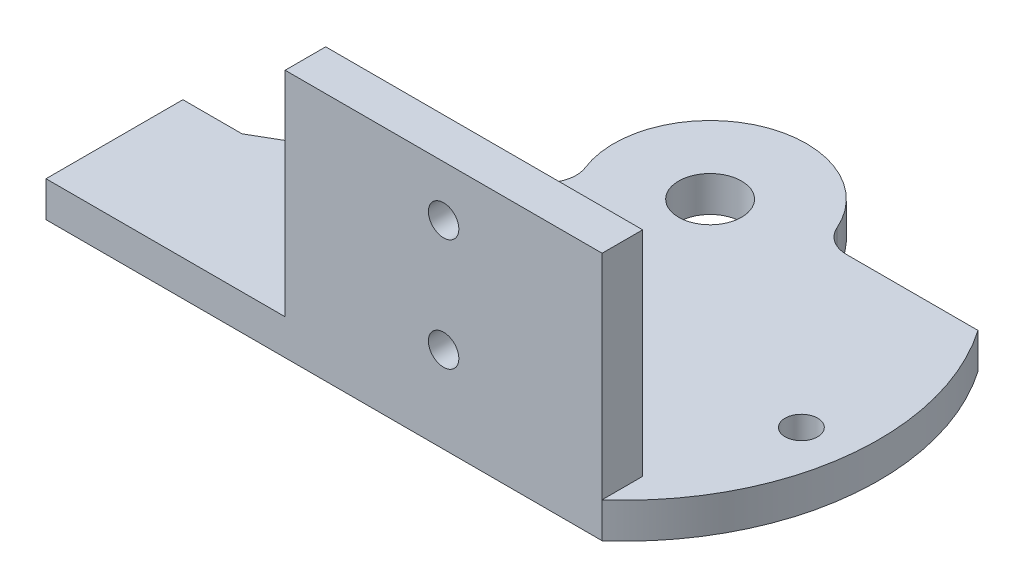
SolidWorks part; units mm, degrees
ref_plane "Alzado" through (0, 0, 0) normal (0, 0, 1) x (1, 0, 0)
ref_plane "Planta" through (0, 0, 0) normal (0, 1, 0) x (1, 0, 0)
ref_plane "Vista lateral" through (0, 0, 0) normal (1, 0, 0) x (0, 0, -1)
sketch "Croquis1" plane through (0, 0, 0) normal (0, 1, 0) x (1, 0, 0)
  line L0 (-35, 32.5) -> (35, -32.5) construction
  line L1 (-35, 32.5) -> (35, 32.5)
  line L2 (-35, 32.5) -> (-35, -32.5)
  line L3 (-35, -32.5) -> (35, -32.5)
  line L4 (35, 32.5) -> (35, -32.5)
  dimension "D1" = 70
  dimension "D2" = 65
extrude "Extruir1" add sketch "Croquis1" along normal blind 3.5
sketch "Croquis2" plane through (0, 3.5, 0) normal (0, 1, 0) x (1, 0, 0)
  line L0 (0, 32.5) -> (0, -32.5) construction
  line L1 (35, 32.5) -> (-35, 32.5) construction
  line L2 (-35, -32.5) -> (35, -32.5) construction
  circle A0 centre (0, -17.5) radius 3.1
  dimension "D1" = 6.2
  dimension "D2" = 15
extrude "Extruir2" cut sketch "Croquis2" against normal blind 5
sketch "Croquis3" plane through (0, 3.5, 0) normal (0, 1, 0) x (1, 0, 0)
  line L0 (0, -32.5) -> (0, 32.5) construction
  line L1 (-35, -32.5) -> (35, -32.5) construction
  line L2 (35, 32.5) -> (-35, 32.5) construction
  line L3 (-32.9868, -32.5) -> (-32.9868, 32.5) construction
  line L4 (-32.9868, 1.5) -> (-12.9615, 1.5)
  line L5 (18.8496, -32.5) -> (18.8496, 32.5) construction
  line L6 (-32.9868, 3.5) -> (18.8496, 3.5) construction
  line L7 (-32.9868, 2) -> (0, 2) construction
  line L8 (-32.9868, 11.5) -> (18.8496, 11.5) construction
  line L9 (0, -17.5) -> (-14.8492, -2.6508) construction
  line L10 (0, -17.5) -> (14.8492, -2.6508) construction
  line L11 (0, 2) -> (18.8496, 2) construction
  line L12 (-32.9868, 2) -> (18.8496, 2) construction
  line L13 (-32.9868, 12) -> (18.8496, 12)
  line L14 (-5.3033, -12.1967) -> (-16.2635, -1.2365) construction
  line L15 (12.9615, 1.5) -> (18.8496, 1.5)
  line L16 (-32.9868, 1.5) -> (18.8496, 1.5) construction
  line L17 (7.9844, -18) -> (22.9946, -18)
  line L18 (-5.9993, -12.2078) -> (-16.6132, -1.5939)
  line L19 (0, -17.5) -> (23, -17.5) construction
  line L20 (7.5, -17.5) -> (23, -17.5) construction
  line L21 (-5.6569, -12.5503) -> (-16.617, -1.5901) construction
  line L22 (7.5, -18) -> (23, -18) construction
  line L23 (-32.9868, 12) -> (-32.9868, 1.5)
  line L24 (18.8496, 12) -> (18.8496, 1.5)
  line L25 (-34.4868, 13.5) -> (20.3496, 13.5)
  line L26 (20.3496, 13.5) -> (20.3496, 0)
  line L27 (17.1464, 0) -> (20.3496, 0)
  line L28 (9.2871, -19.5) -> (24.4182, -19.5)
  line L29 (-7.9812, -12.3473) -> (-18.6805, -1.6479)
  line L30 (-34.4868, 0) -> (-17.1464, 0)
  line L31 (-34.4868, 13.5) -> (-34.4868, 0)
  circle A0 centre (0, -17.5) radius 21 construction
  circle A1 centre (0, -17.5) radius 7.5 construction
  arc A2 (-12.9615, 1.5) -> (-16.6132, -1.5939) centre (0, -17.5) ccw
  circle A3 centre (0, -17.5) radius 23 construction
  arc A4 (-5.9993, -12.2078) -> (7.9844, -18) centre (0, -17.5) ccw
  arc A5 (22.9946, -18) -> (12.9615, 1.5) centre (0, -17.5) ccw
  arc A6 (24.4182, -19.5) -> (17.1464, 0) centre (0, -17.5) ccw
  arc A7 (-7.9812, -12.3473) -> (9.2871, -19.5) centre (0, -17.5) ccw
  arc A8 (-17.1464, 0) -> (-18.6805, -1.6479) centre (0, -17.5) ccw
  dimension "D3" = 42
  dimension "D8" = 15
  dimension "D9" = 46
  dimension "D14" = 0.5
  dimension "D2" = 51.8364
  dimension "D6" = 90
  dimension "D7" = 45
  dimension "D1" = 32.9868
  dimension "D4" = 1.5
  dimension "D5" = 9.5
  dimension "D10" = 2
  dimension "D11" = 0.5
  dimension "D12" = 0.5
  dimension "D13" = 0.5
  dimension "D15" = 1.5
extrude "Extruir3" add sketch "Croquis3" along normal blind 10
sketch "Croquis4" plane through (0, 3.5, 0) normal (0, 1, 0) x (1, 0, 0)
  line L0 (-34.4868, 0) -> (-17.1464, 0) construction
  line L1 (-34.4868, 13.5) -> (-34.4868, 0) construction
  line L2 (20.3496, 13.5) -> (-34.4868, 13.5) construction
  line L3 (20.3496, 0) -> (20.3496, 13.5) construction
  line L4 (17.1464, 0) -> (20.3496, 0) construction
  line L5 (9.2871, -19.5) -> (24.4182, -19.5) construction
  line L6 (-18.6805, -1.6479) -> (-7.9812, -12.3473) construction
  line L7 (-34.4868, 0) -> (-17.1464, 0)
  line L8 (-34.4868, 13.5) -> (-34.4868, 0)
  line L9 (20.3496, 13.5) -> (-34.4868, 13.5)
  line L10 (20.3496, 0) -> (20.3496, 13.5)
  line L11 (17.1464, 0) -> (20.3496, 0)
  line L12 (9.2871, -19.5) -> (24.4182, -19.5)
  line L13 (-18.6805, -1.6479) -> (-7.9812, -12.3473)
  arc A0 (-17.1464, 0) -> (-18.6805, -1.6479) centre (0, -17.5) ccw construction
  arc A1 (24.4182, -19.5) -> (17.1464, 0) centre (0, -17.5) ccw construction
  arc A2 (-7.9812, -12.3473) -> (9.2871, -19.5) centre (0, -17.5) ccw construction
  arc A3 (-17.1464, 0) -> (-18.6805, -1.6479) centre (0, -17.5) ccw
  arc A4 (24.4182, -19.5) -> (17.1464, 0) centre (0, -17.5) ccw
  arc A5 (-7.9812, -12.3473) -> (9.2871, -19.5) centre (0, -17.5) ccw
extrude "Extruir4" cut sketch "Croquis4" against normal blind 10 flip side to cut
fillet "Redondeo1" radius 3 4 edges at (9.2871, 6.75, 19.5) (-7.9812, 6.75, 12.3473) (7.9844, 8.5, 18) (-5.9993, 8.5, 12.2078)
sketch "Croquis5" plane through (0, 0, 0) normal (0, -1, 0) x (1, 0, 0)
  line L0 (-18.6805, 1.6479) -> (-9.5151, 10.8133) construction
  line L1 (-34.4868, 0) -> (-17.1464, 0) construction
  line L2 (-18.6805, 1.6479) -> (-14.4379, 5.8906)
  line L3 (-24.4498, 0) -> (-17.1464, 0)
  line L4 (20.3496, 0) -> (20.3496, -13.5) construction
  line L5 (17.1464, 0) -> (20.3496, 0) construction
  line L6 (20.3496, 0) -> (20.3496, -13.5)
  line L7 (17.1464, 0) -> (20.3496, 0)
  arc A0 (-14.4379, 5.8906) -> (-24.4498, 0) centre (-18.6805, 1.6479) ccw
  arc A1 (-18.6805, 1.6479) -> (-17.1464, 0) centre (0, 17.5) ccw construction
  arc A2 (-18.6805, 1.6479) -> (-17.1464, 0) centre (0, 17.5) ccw
  arc A3 (24.4182, 19.5) -> (20.3496, -13.5) centre (3.8531, 5.2847) cw
  arc A4 (17.1464, 0) -> (24.4182, 19.5) centre (0, 17.5) ccw construction
  arc A5 (17.1464, 0) -> (24.4182, 19.5) centre (0, 17.5) ccw
  dimension "D1" = 12
  dimension "D2" = 25
extrude "Extruir5" add sketch "Croquis5" against normal up to surface (13.5 mm away) up to face at (-1.8278, 13.5, 5.5887)
chamfer "Chaflán1" distance 5 angle 45 2 edges at (-14.4379, 6.75, 5.8906) (-24.4498, 6.75, 0) first distance on face at (-20.5835, 6.75, 4.8823) first distance on face at (-29.4683, 6.75, 0)
sketch "Croquis6" plane through (0, 13.5, 0) normal (0, 1, 0) x (1, 0, 0)
  line L7 (-34.4868, 13.5) -> (-34.4868, 0)
  line L8 (-34.4868, 0) -> (-28.6614, 0)
  line L9 (-28.6614, 0) -> (-24.6424, -2.3231)
  line L10 (-16.83, -7.3554) -> (-11.7523, -8.5761)
  line L11 (-11.7523, -8.5761) -> (-9.5151, -10.8133)
  line L12 (11.4564, -19.5) -> (24.4182, -19.5)
  line L13 (20.3496, 13.5) -> (-34.4868, 13.5)
  line L14 (-34.4868, 13.5) -> (-34.4868, 0)
  line L15 (-34.4868, 0) -> (-28.6614, 0)
  line L16 (-28.6614, 0) -> (-24.6424, -2.3231)
  line L17 (-16.83, -7.3554) -> (-11.7523, -8.5761)
  line L18 (-11.7523, -8.5761) -> (-9.5151, -10.8133)
  line L19 (11.4564, -19.5) -> (24.4182, -19.5)
  line L20 (20.3496, 13.5) -> (-34.4868, 13.5)
  arc A5 (-24.6424, -2.3231) -> (-16.83, -7.3554) centre (-18.6805, -1.6479) ccw
  arc A6 (-8.8437, -14.0303) -> (-9.5151, -10.8133) centre (-11.6365, -12.9346) ccw
  arc A7 (-8.8437, -14.0303) -> (8.7069, -21.3) centre (0, -17.5) ccw
  arc A8 (11.4564, -19.5) -> (8.7069, -21.3) centre (11.4564, -22.5) ccw
  arc A9 (24.4182, -19.5) -> (20.3496, 13.5) centre (3.8531, -5.2847) ccw
  arc A10 (-24.6424, -2.3231) -> (-16.83, -7.3554) centre (-18.6805, -1.6479) ccw
  arc A11 (-8.8437, -14.0303) -> (-9.5151, -10.8133) centre (-11.6365, -12.9346) ccw
  arc A12 (-8.8437, -14.0303) -> (8.7069, -21.3) centre (0, -17.5) ccw
  arc A13 (11.4564, -19.5) -> (8.7069, -21.3) centre (11.4564, -22.5) ccw
  arc A14 (24.4182, -19.5) -> (20.3496, 13.5) centre (3.8531, -5.2847) ccw
  dimension "D1" = 0
extrude "Extruir6" add sketch "Croquis6" along normal blind 3.5 separate body
sketch "Croquis7" plane through (0, 17, 0) normal (0, 1, 0) x (1, 0, 0)
  line L0 (20.3496, 13.5) -> (-34.4868, 13.5) construction
  circle A0 centre (-20, -2.5) radius 1.6
  circle A1 centre (24, -2.5) radius 1.6
  dimension "D1" = 3.2
  dimension "D2" = 16
  dimension "D3" = 20
  dimension "D4" = 24
extrude "Extruir7" cut sketch "Croquis7" against normal through all
sketch "Croquis8" plane through (0, 17, 0) normal (0, 1, 0) x (1, 0, 0)
  circle A0 centre (0, -17.5) radius 3.1 construction
  circle A1 centre (0, -17.5) radius 3.1
extrude "Extruir8" cut sketch "Croquis8" against normal blind 5
sketch "Croquis9" plane through (0, 13.5, 0) normal (0, 1, 0) x (1, 0, 0)
  line L0 (18.8496, 1.5) -> (18.8496, 12) construction
  line L1 (18.8496, 1.5) -> (18.8496, 12)
  line L2 (19.5496, 1.5) -> (19.5496, 12)
  line L3 (18.8496, 12) -> (19.5496, 12)
  line L4 (18.8496, 1.5) -> (19.5496, 1.5)
  dimension "D1" = 0.7
extrude "Extruir9" cut sketch "Croquis9" against normal up to surface (10 mm away) up to face at (-1.6185, 3.5, 4.8365)
sketch "Croquis10" plane through (19.5496, 0, 0) normal (-1, 0, 0) x (0, 0, 1)
  line L0 (-5.875, 13.5) -> (-5.875, 3.5) construction
  line L3 (-1.5, 13.5) -> (-12, 13.5) construction
  line L4 (-12, 3.5) -> (-12, 13.5) construction
  line L5 (-5.875, 13.5) -> (-12, 3.5) construction
  line L6 (-12, 3.5) -> (-1.5, 3.5) construction
  line L7 (-8.9375, 8.5) -> (-12, 13.5) construction
  line L8 (19.5, 13.5) -> (-13.5, 13.5) construction
  line L10 (-7.4062, 11) -> (-10.4687, 11)
  line L11 (-7.4062, 11) -> (-7.4062, 6)
  line L12 (-7.4062, 6) -> (-10.4687, 6)
  line L13 (-10.4687, 11) -> (-10.4687, 6)
  dimension "D1" = 6.125
  dimension "D2" = 5
  dimension "D3" = 3.0625
extrude "Extruir10" cut sketch "Croquis10" against normal blind 10 and the other way through all
delete or keep bodies "Sólido-Eliminar1" type delete bodies bodies 111
sketch "Croquis11" plane through (0, 0, -13.5) normal (0, 0, -1) x (-1, 0, 0)
  line L0 (34.4868, 17) -> (34.4868, 38.056)
  line L2 (-20.3496, 38.056) -> (-20.3496, 17)
  line L3 (-20.3496, 17) -> (34.4868, 17)
  line L4 (34.4868, 38.056) -> (-20.3496, 38.056)
  dimension "D2" = 21.056
extrude "Saliente-Extruir1" add sketch "Croquis11" against normal blind 4
sketch "Croquis15" plane through (0, 0, -9.5) normal (0, 0, 1) x (1, 0, 0)
  line L1 (-34.4868, 38.056) -> (-10.9056, 38.056)
  line L2 (-34.4868, 38.056) -> (-34.4868, 17)
  line L3 (-34.4868, 17) -> (-10.9056, 17)
  line L4 (-10.9056, 38.056) -> (-10.9056, 17)
extrude "Cortar-Extruir3" cut sketch "Croquis15" against normal blind 10
sketch "Croquis16" plane through (0, 0, -9.5) normal (0, 0, 1) x (1, 0, 0)
  line L0 (4.722, 17) -> (4.722, 38.056) construction
  line L1 (20.3496, 17) -> (-10.9056, 17) construction
  line L2 (-10.9056, 38.056) -> (20.3496, 38.056) construction
  circle A0 centre (4.722, 33.056) radius 1.5
  circle A1 centre (4.722, 22) radius 1.5
  dimension "D1" = 3
  dimension "D2" = 3
  dimension "D3" = 5
  dimension "D4" = 5
extrude "Cortar-Extruir4" cut sketch "Croquis16" against normal blind 10
ref_plane "Plano1" through (0, 0, -23.5) normal (0, 0, -1) x (-1, 0, 0)
mirror "Simetría1" about plane through (0, 0, -23.5) normal (0, 0, -1) of bodies 119
sketch "Croquis17" plane through (0, 17, 0) normal (0, 1, 0) x (1, 0, 0)
  line L1 (-42.9317, 16.4383) -> (45.6259, 16.4383)
  line L2 (-42.9317, 16.4383) -> (-42.9317, -29.7491)
  line L3 (-42.9317, -29.7491) -> (45.6259, -29.7491)
  line L4 (45.6259, 16.4383) -> (45.6259, -29.7491)
extrude "Cortar-Extruir5" cut sketch "Croquis17" against normal blind 10 and the other way blind 59
